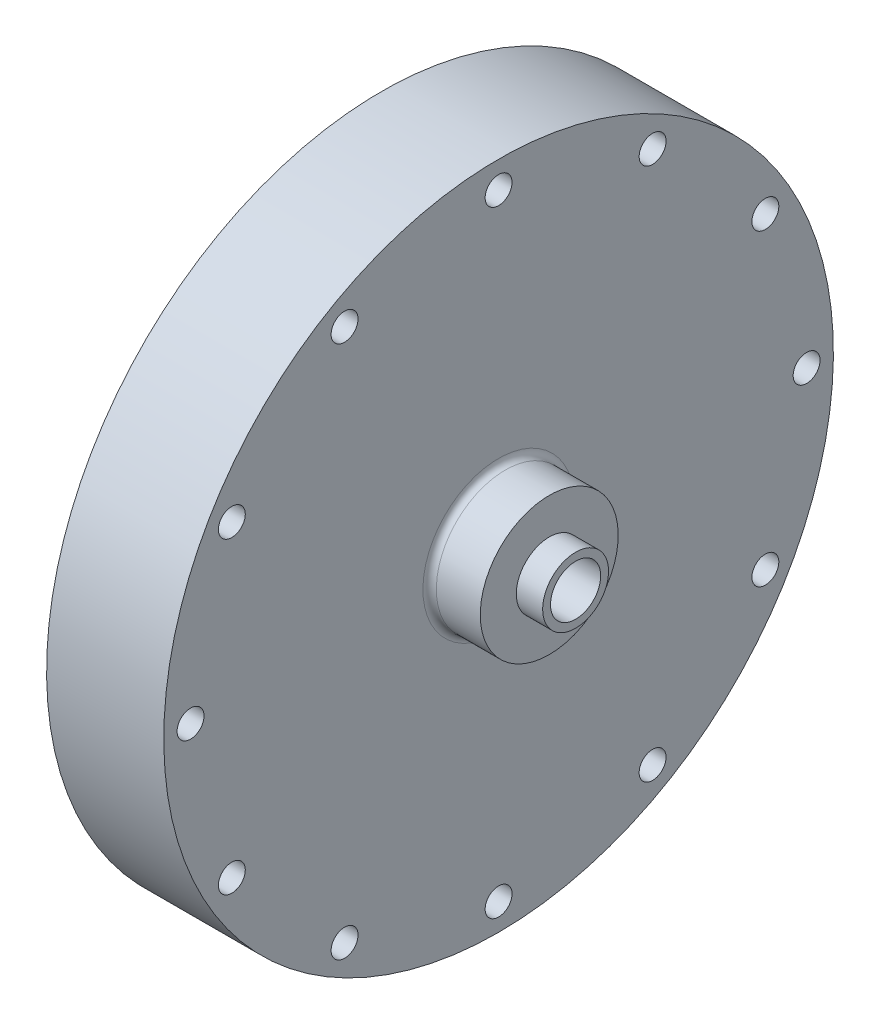
SolidWorks part; units mm, degrees
material "7075-T6 (SN)"
ref_plane "Front Plane" through (0, 0, 0) normal (0, 0, 1) x (1, 0, 0)
ref_plane "Top Plane" through (0, 0, 0) normal (0, 1, 0) x (1, 0, 0)
ref_plane "Right Plane" through (0, 0, 0) normal (1, 0, 0) x (0, 0, -1)
sketch "Sketch2" plane through (0, 0, 0) normal (0, 0, 1) x (1, 0, 0)
  line L0 (9.525, 0) -> (165.0115, 0) construction
  line L5 (41.355, 13.081) -> (41.355, 6.2484)
  line L6 (31.75, 13.081) -> (41.355, 13.081)
  line L7 (41.355, 6.2484) -> (46.355, 6.2484)
  line L8 (46.355, 6.2484) -> (46.355, 0)
  line L9 (9.525, 0) -> (46.355, 0)
  line L16 (9.525, 0) -> (9.525, 63.5)
  line L18 (31.75, 63.5) -> (31.75, 13.081)
  line L19 (31.75, 63.5) -> (9.525, 63.5)
  dimension "D1" = 63.5
  dimension "D2" = 36.83
  dimension "D4" = 13.081
  dimension "D5" = 22.225
  dimension "D7" = 6.2484
  dimension "D8" = 5
revolve "Main Structure" add sketch "Sketch2" angle 360 about L0
cosmetic thread "Cosmetic Thread1" parameters "D2"=23.1953
sketch "Sketch3" plane through (46.355, 0, 0) normal (1, 0, 0) x (0, 0, -1)
  circle A0 centre (0, 0) radius 4.7625
  dimension "D1" = 9.525
extrude "Oxidizer Inlet Hole" cut sketch "Sketch3" against normal through all
sketch "Sketch4" plane through (31.75, 0, 0) normal (-1, 0, 0) x (0, 0, 1)
  circle A0 centre (0, 0) radius 58.42 construction
  circle A1 centre (0, -58.42) radius 2.146
  circle A2 centre (-29.21, -50.5932) radius 2.146
  circle A3 centre (-50.5932, -29.21) radius 2.146
  circle A4 centre (-58.42, 0) radius 2.146
  circle A5 centre (-50.5932, 29.21) radius 2.146
  circle A6 centre (-29.21, 50.5932) radius 2.146
  circle A7 centre (0, 58.42) radius 2.146
  circle A8 centre (29.21, 50.5932) radius 2.146
  circle A9 centre (50.5932, 29.21) radius 2.146
  circle A10 centre (58.42, 0) radius 2.146
  circle A11 centre (50.5932, -29.21) radius 2.146
  circle A12 centre (29.21, -50.5932) radius 2.146
  point P29 (0, 0)
  dimension "D1" = 12
  dimension "D2" = 116.84
hole_wizard "Flange Holes" positions "Sketch7" profile "Sketch8" hole size "#7" standard "ANSI Inch" end condition up to next
sketch "Sketch7" plane through (31.75, 0, 0) normal (-1, 0, 0) x (0, 0, 1)
  point P0 (0, -58.42)
  point P3 (-29.21, -50.5932)
  point P6 (-50.5932, -29.21)
  point P9 (-58.42, 0)
  point P12 (-50.5932, 29.21)
  point P15 (-29.21, 50.5932)
  point P18 (0, 58.42)
  point P21 (29.21, 50.5932)
  point P24 (50.5932, 29.21)
  point P27 (58.42, 0)
  point P30 (50.5932, -29.21)
  point P33 (29.21, -50.5932)
sketch "Sketch8" plane through (31.75, -58.42, 0) normal (0, 1, 0) x (0, 0, -1)
  line L0 (0, 0) -> (0, 22.225)
  line L1 (0, 22.225) -> (2.5527, 22.225)
  line L2 (2.5527, 22.225) -> (2.5527, 0)
  line L5 (2.5527, 0) -> (0, 0)
  line L11 (0, -6.35) -> (0, 107.95) construction
  dimension "Thru Hole Dia." = 5.1054
  dimension "Thru Hole Depth" = 22.225
sketch "Sketch9" plane through (9.525, 0, 0) normal (-1, 0, 0) x (0, 0, 1)
  line L0 (0, 0) -> (-67.6727, 18.1329) construction
  line L1 (0, 0) -> (-58.42, 0) construction
  circle A0 centre (0, 0) radius 58.42 construction
  circle A1 centre (-56.4294, 15.1202) radius 2.9451
  circle A2 centre (56.4294, -15.1202) radius 2.9451
  point P14 (0, 0)
  dimension "D1" = 15
  dimension "D2" = 2
hole_wizard "Dowel Holes" positions "Sketch10" profile "Sketch11" hole size "3/16" standard "ANSI Inch"
sketch "Sketch10" plane through (9.525, 0, 0) normal (-1, 0, 0) x (0, 0, 1)
  point P0 (56.4294, -15.1202)
  point P3 (-56.4294, 15.1202)
sketch "Sketch11" plane through (9.525, -15.1202, 56.4294) normal (0, 1, 0) x (0, 0, 1)
  line L0 (0, 0) -> (0, 7.7808)
  line L1 (0, 7.7808) -> (2.3812, 6.35)
  line L2 (2.3812, 6.35) -> (2.3812, 0)
  line L5 (2.3812, 0) -> (0, 0)
  line L10 (0, 7.7808) -> (-2.3812, 6.35) construction
  line L11 (0, -6.35) -> (0, 107.95) construction
  dimension "Hole Dia." = 4.7625
  dimension "Hole Depth" = 6.35
  dimension "Drill Angle" = 118
sketch "Sketch12" plane through (9.525, 0, 0) normal (-1, 0, 0) x (0, 0, 1)
  circle A0 centre (0, 0) radius 28.575
  dimension "D1" = 57.15
extrude "Cut-Extrude2" cut sketch "Sketch12" against normal blind 9.525
ref_plane "Plane1" through (9.525, 0, 0) normal (-1, 0, 0) x (0, 0, 1)
ref_plane "Plane4" through (19.05, 0, 0) normal (-1, 0, 0) x (0, 0, 1)
sketch "Sketch16" plane through (19.05, 0, 0) normal (-1, 0, 0) x (0, 0, 1)
  circle A0 centre (0, 0) radius 28.575
  dimension "D1" = 57.15
ref_plane "Plane2" through (30.48, 0, 0) normal (-1, 0, 0) x (0, 0, 1)
sketch "Sketch17" plane through (30.48, 0, 0) normal (-1, 0, 0) x (0, 0, 1)
  circle A0 centre (0, 0) radius 4.7625
  dimension "D1" = 9.525
loft "Internal Flow Path Loft Cut" cut profiles "Sketch16", "Sketch17" connector at (19.05, 0, 28.575) connector at (30.48, 0, 4.7625)
sketch "Sketch18" plane through (9.525, 0, 0) normal (-1, 0, 0) x (0, 0, 1)
  circle A0 centre (0, 0) radius 33.3375
  circle A1 centre (33.3375, 0) radius 1.5042
  dimension "D1" = 66.675
hole_wizard "#4-40 Tapped Hole1" positions "Sketch19" profile "Sketch20" tap size "#4-40" standard "ANSI Inch"
sketch "Sketch19" plane through (9.525, 0, 0) normal (-1, 0, 0) x (0, 0, 1)
  point P0 (33.3375, 0)
sketch "Sketch20" plane through (9.525, 0, 33.3375) normal (0, 1, 0) x (0, 0, 1)
  line L0 (0, 0) -> (0, 13.8872)
  line L1 (0, 13.8872) -> (1.1303, 13.208)
  line L2 (1.1303, 13.208) -> (1.1303, 0)
  line L5 (1.1303, 0) -> (0, 0)
  line L10 (0, 13.8872) -> (-1.1303, 13.208) construction
  line L11 (0, -6.35) -> (0, 107.95) construction
  dimension "Tap Drill Dia." = 2.2606
  dimension "Tap Drill Depth" = 13.208
  dimension "Drill Angle" = 118
cosmetic thread "Hole Thread1" parameters "D1"=9.398, "D2"=2.8448
pattern_circular "CirPattern1" count 8 over 360 about axis through (30.48, 0, 0) along (1, 0, 0) of "#4-40 Tapped Hole1"
fillet "Fillet1" radius 1.27 1 edges at (31.75, -13.081, 0)
